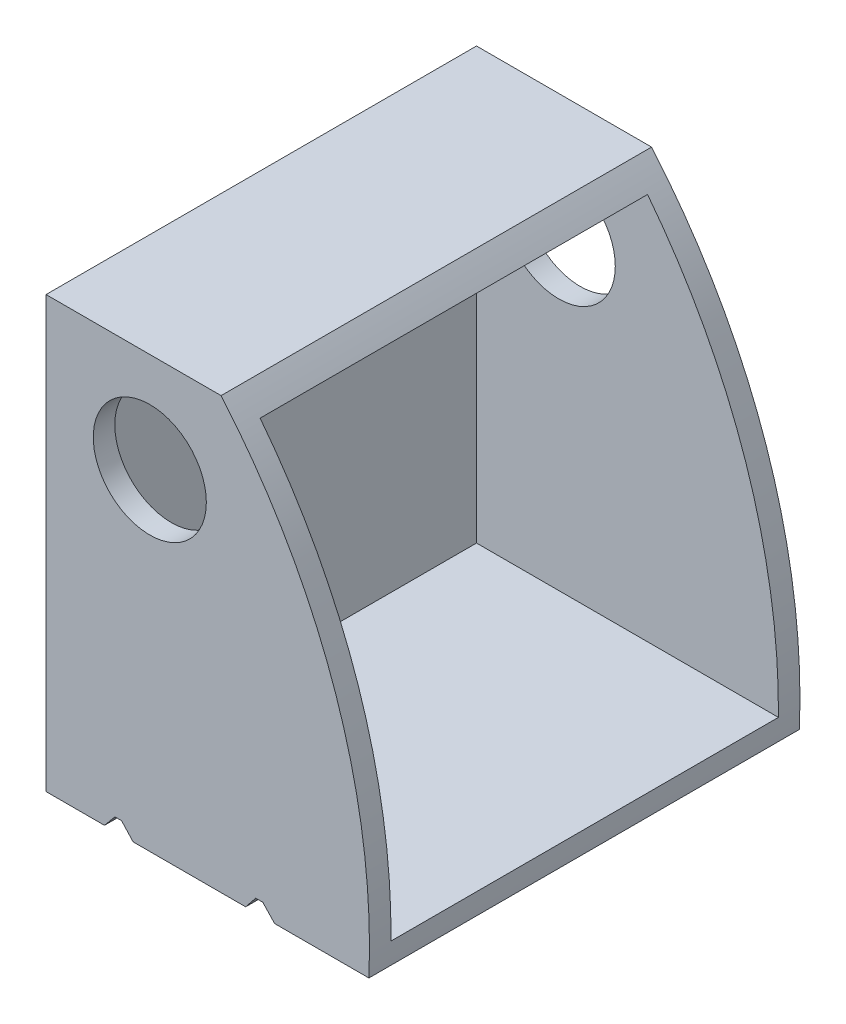
SolidWorks part; units mm, degrees
ref_plane "Front Plane" through (0, 0, 0) normal (0, 0, 1) x (1, 0, 0)
ref_plane "Top Plane" through (0, 0, 0) normal (0, 1, 0) x (1, 0, 0)
ref_plane "Right Plane" through (0, 0, 0) normal (1, 0, 0) x (0, 0, -1)
sketch "Sketch1" plane through (0, 0, 0) normal (0, 0, 1) x (1, 0, 0)
  line L1 (-10.0968, 187.4107) -> (71.2368, 187.4107)
  line L2 (-10.0968, 187.4107) -> (-10.0968, -12.5893)
  line L3 (-10.0968, -12.5893) -> (139.9032, -12.5893)
  arc A0 (71.2368, 187.4107) -> (139.9032, -12.5893) centre (-148.7788, 0.0845) cw
  dimension "D1" = 200
  dimension "D2" = 150
extrude "Boss-Extrude1" add sketch "Sketch1" along normal blind 200
shell "Shell1" thickness 10 removed face at (115.046, 90.6641, 100)
sketch "Sketch2" plane through (0, 0, 200) normal (0, 0, 1) x (1, 0, 0)
  circle A0 centre (38.1122, 141.0119) radius 26.2674
extrude "Cut-Extrude1" cut sketch "Sketch2" against normal blind 200
sketch "Sketch3" plane through (0, 0, 200) normal (0, 0, 1) x (1, 0, 0)
  line L0 (17.0515, -12.5893) -> (21.8851, -6.7583)
  line L1 (-10.0968, -12.5893) -> (139.9032, -12.5893) construction
  line L2 (21.8851, -6.7583) -> (24.9924, -6.7583)
  line L3 (24.9924, -6.7583) -> (30.3439, -12.5893)
  line L4 (30.3439, -12.5893) -> (17.0515, -12.5893)
  line L5 (82.6504, -12.5893) -> (87.3114, -6.7583)
  line L6 (87.3114, -6.7583) -> (90.5913, -6.7583)
  line L7 (90.5913, -6.7583) -> (96.1154, -12.5893)
  line L8 (96.1154, -12.5893) -> (82.6504, -12.5893)
extrude "Cut-Extrude2" cut sketch "Sketch3" against normal blind 200
